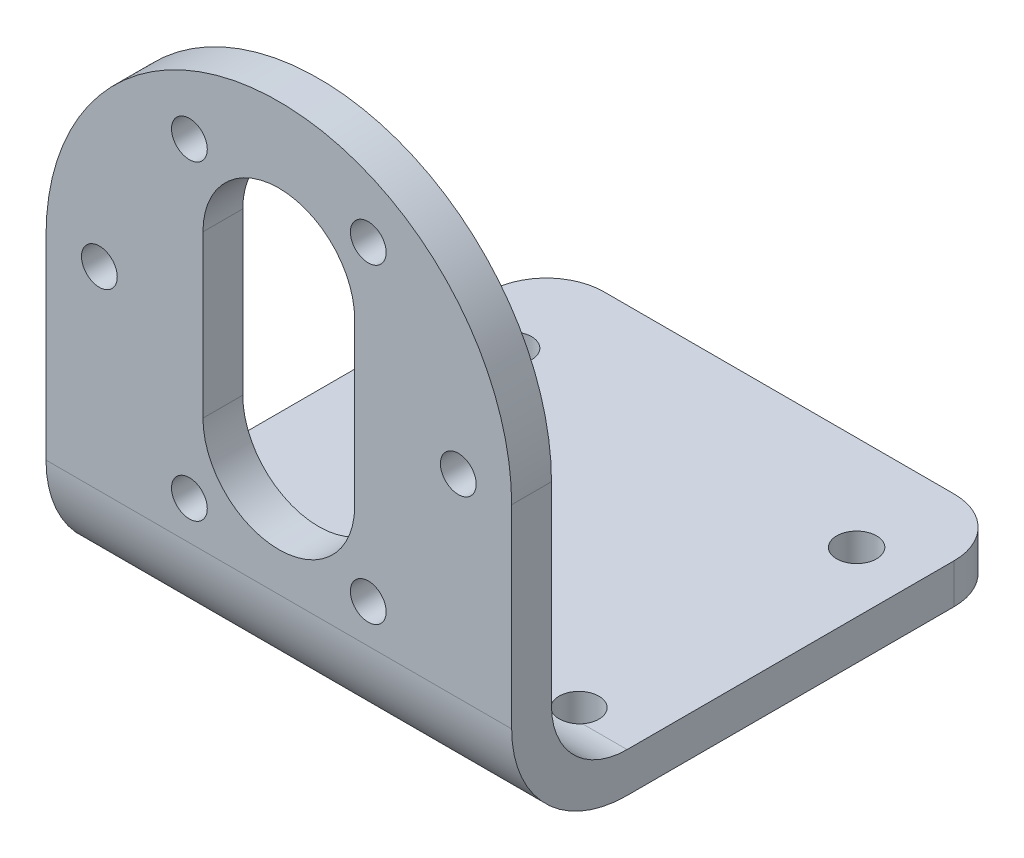
SolidWorks part; units mm, degrees
ref_plane "Front Plane" through (0, 0, 0) normal (0, 0, 1) x (1, 0, 0)
ref_plane "Top Plane" through (0, 0, 0) normal (0, 1, 0) x (1, 0, 0)
ref_plane "Right Plane" through (0, 0, 0) normal (1, 0, 0) x (0, 0, -1)
sketch "Sketch1" plane through (0, 0, 0) normal (0, 1, 0) x (1, 0, 0)
  line L1 (-47.1412, -7.433) -> (-6.7912, -7.433)
  line L2 (-47.1412, -7.433) -> (-47.1412, -50.783)
  line L3 (-47.1412, -50.783) -> (-6.7912, -50.783)
  line L4 (-6.7912, -7.433) -> (-6.7912, -50.783)
extrude "Boss-Extrude1" add sketch "Sketch1" along normal blind 47
sketch "Sketch3" plane through (0, 0, 50.783) normal (0, 0, 1) x (1, 0, 0)
  line L6 (-47.1412, 26.825) -> (-47.1412, 47)
  line L7 (-47.1412, 47) -> (-6.7912, 47)
  line L8 (-6.7912, 26.825) -> (-6.7912, 47)
  arc A1 (-6.7912, 26.825) -> (-47.1412, 26.825) centre (-26.9662, 26.825) ccw
  line M2 (-6.7912, 0) -> (-6.7912, 47)
  line M3 (-6.7912, 47) -> (-47.1412, 47)
  line M4 (-47.1412, 47) -> (-47.1412, 0)
extrude "Cut-Extrude2" cut sketch "Sketch3" against normal blind 102 contours A1 L7 M4 | A1 M2 M3 region at (-11.2977, 42.4936, 50.783) region at (-42.6348, 42.4936, 50.783)
fillet "Fillet1" radius 10 1 edges at (-26.9662, 0, 50.783)
sketch "Sketch5" plane through (-47.1412, 0, 0) normal (-1, 0, 0) x (0, 0, 1)
  line L0 (7.433, 0) -> (-6.6658, 0)
  line L1 (-6.6658, 0) -> (-6.6658, 3.45)
  line L2 (50.783, 47) -> (50.783, 59.7784)
  line L3 (50.783, 59.7784) -> (47.333, 59.7784)
  line L5 (-6.6658, 3.45) -> (36.5956, 3.45)
  line L6 (-6.6658, 3.45) -> (-6.6658, 59.7784)
  line L7 (-6.6658, 59.7784) -> (47.333, 59.7784)
  line L8 (47.333, 17.5785) -> (47.333, 59.7784)
  line L9 (36.5956, 3.45) -> (40.783, 3.45)
  line L12 (47.333, 10) -> (47.333, 17.5785)
  arc A1 (40.783, 3.45) -> (47.333, 10) centre (40.783, 10) ccw
  line M2 (50.783, 26.825) -> (7.433, 26.825)
  line M3 (7.433, 26.825) -> (7.433, 0)
extrude "Cut-Extrude3" cut sketch "Sketch5" against normal blind 102 contours L8 L7 L6 L5 M2 M3 | L5 L8 M2 M3 region at (-47.1412, 15.2394, 27.1987) region at (-47.1412, 38.9007, 17.2162)
fillet "Fillet2" radius 5 2 edges at (-6.7912, 1.725, 7.433) (-47.1412, 1.725, 7.433)
sketch "Sketch6" plane through (0, 3.45, 0) normal (0, 1, 0) x (1, 0, 0)
  line L0 (-27.9141, -7.433) -> (-27.9141, -13.933)
  line L1 (-42.1412, -7.433) -> (-11.7912, -7.433) construction
  line L2 (-47.1412, -24.2783) -> (-43.6412, -24.2783)
  line L3 (-47.1412, -12.433) -> (-47.1412, -40.783) construction
  line L4 (-6.7912, -25.5422) -> (-10.2912, -25.5422)
  line L5 (-6.7912, -12.433) -> (-6.7912, -40.783) construction
  line L6 (-43.6412, -24.2783) -> (-43.6412, -13.933)
  line L7 (-43.6412, -13.933) -> (-10.2912, -13.933)
  line L8 (-10.2912, -13.933) -> (-10.2912, -45.493)
  line L9 (-10.2912, -45.493) -> (-43.6412, -45.493)
  line L10 (-43.6412, -45.493) -> (-43.6412, -24.2783)
  line L11 (-41.9112, -17.393) -> (-41.9112, -37.993)
  line L12 (-12.0212, -17.393) -> (-12.0212, -37.993)
  circle A0 centre (-41.9112, -15.663) radius 1.73
  circle A1 centre (-12.0212, -15.663) radius 1.73
  circle A2 centre (-41.9112, -39.723) radius 1.73
  circle A3 centre (-12.0212, -39.723) radius 1.73
  line M12 (-47.1412, -40.783) -> (-6.7912, -40.783)
extrude "Cut-Extrude4" cut sketch "Sketch6" against normal blind 102 and the other way blind 102 contours A3 M12 | A3 M12 | A2 M12 | A2 M12 | A1 | A0 region at (-41.9112, 3.45, 15.663) region at (-41.9112, 3.45, 39.5133) region at (-41.9112, 3.45, 41.056) region at (-12.0212, 3.45, 15.663) region at (-12.0212, 3.45, 41.056) region at (-12.0212, 3.45, 39.5133)
sketch "Sketch7" plane through (0, 0, 50.783) normal (0, 0, 1) x (1, 0, 0)
  line L0 (-47.1412, 21.9829) -> (-33.5412, 21.9829)
  line L2 (-33.5412, 33.925) -> (-33.5412, 19.945)
  line L4 (-20.3912, 33.925) -> (-20.3912, 19.945)
  line L5 (-47.1412, 26.825) -> (-47.1412, 10) construction
  line L6 (-20.3912, 20.4169) -> (-6.7912, 20.4169)
  line L7 (-6.7912, 26.825) -> (-6.7912, 10) construction
  line L8 (-26.9662, 47) -> (-26.9662, 40.5)
  arc A0 (-6.7912, 26.825) -> (-47.1412, 26.825) centre (-26.9662, 26.825) ccw construction
  arc A1 (-20.3912, 33.925) -> (-33.5412, 33.925) centre (-26.9662, 33.925) ccw
  arc A2 (-33.5412, 19.945) -> (-20.3912, 19.945) centre (-26.9662, 19.945) ccw
extrude "Cut-Extrude5" cut sketch "Sketch7" against normal blind 102 contours L2 A2 L4 A1 region at (-26.9662, 26.935, 50.783)
sketch "Sketch8" plane through (0, 0, 50.783) normal (0, 0, 1) x (1, 0, 0)
  line L4 (-40.9662, 26.825) -> (-44.0662, 26.825)
  line L5 (-12.9662, 26.825) -> (-9.8662, 26.825)
  arc A0 (-33.84, 39.0214) -> (-20.0924, 39.0214) centre (-26.9662, 26.825) ccw
  arc A1 (-35.4887, 41.6499) -> (-18.4437, 41.6499) centre (-26.9662, 26.825) ccw
  arc A2 (-20.0924, 14.6286) -> (-20.1019, 14.616) centre (-26.9662, 19.725) cw
  arc A3 (-33.8306, 39.034) -> (-33.84, 39.0214) centre (-26.9662, 33.925) ccw
  circle A4 centre (-34.7162, 40.3061) radius 1.55
  circle A5 centre (-19.2162, 40.3061) radius 1.55
  circle A6 centre (-19.2162, 13.3439) radius 1.55
  arc A7 (-20.0924, 39.0214) -> (-20.1019, 39.034) centre (-26.9662, 33.925) ccw
  circle A8 centre (-34.7162, 13.3439) radius 1.55
  arc A9 (-33.8306, 14.616) -> (-33.84, 14.6286) centre (-26.9662, 19.725) cw
  circle A10 centre (-42.5162, 26.825) radius 1.55
  circle A11 centre (-11.4162, 26.825) radius 1.55
  dimension "D1" = 15.5
extrude "Cut-Extrude6" cut sketch "Sketch8" against normal blind 102 contours A8 | A6 | L5 A11 | L5 A11 | L4 A10 | L4 A10 | A4 | A5 A4 region at (-42.5162, 26.1672, 50.783) region at (-42.5162, 27.4828, 50.783) region at (-34.7162, 40.3061, 50.783) region at (-34.7162, 13.3439, 50.783) region at (-19.2162, 13.3439, 50.783) region at (-11.4162, 26.1672, 50.783) region at (-11.4162, 27.4828, 50.783) region at (-19.2162, 40.3061, 50.783)
